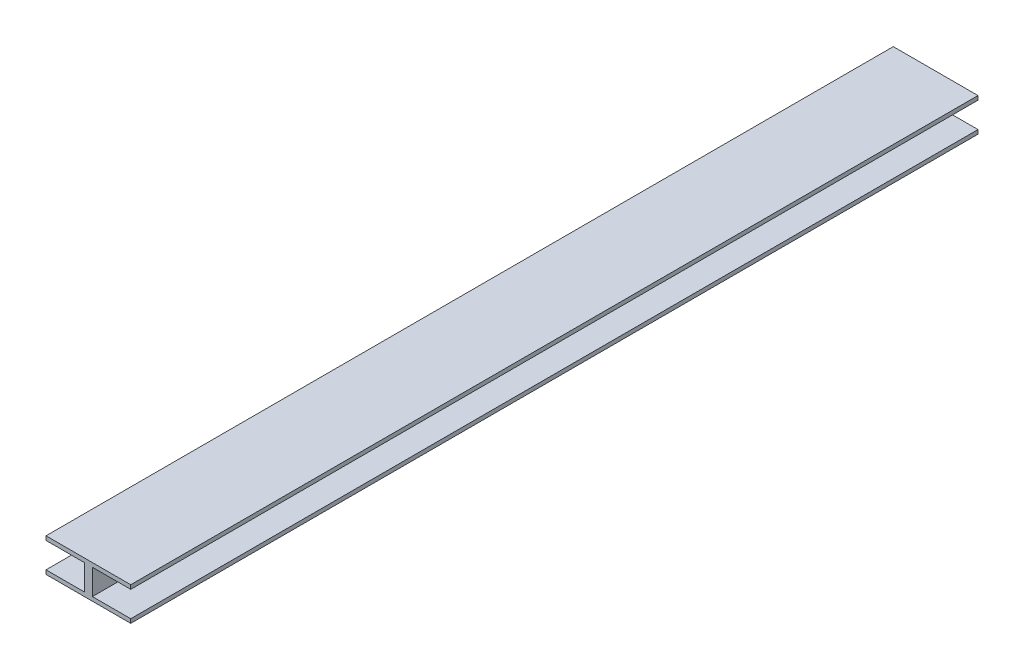
SolidWorks part; units mm, degrees
material "Acero al carbono no aleado"
ref_plane "Alzado" through (0, 0, 0) normal (0, 0, 1) x (1, 0, 0)
ref_plane "Planta" through (0, 0, 0) normal (0, 1, 0) x (1, 0, 0)
ref_plane "Vista lateral" through (0, 0, 0) normal (1, 0, 0) x (0, 0, -1)
sketch "Croquis1" plane through (0, 0, 0) normal (0, 0, 1) x (1, 0, 0)
  line L0 (0, 19.7625) -> (-50, 19.7625)
  line L1 (0, 19.7625) -> (0, -19.7625)
  line L2 (0, -19.7625) -> (-50, -19.7625)
  line L3 (-4.7625, -15) -> (-50, -15)
  line L4 (-4.7625, 15) -> (-4.7625, -15)
  line L5 (-4.7625, 15) -> (-50, 15)
  line L6 (-50, -19.7625) -> (-50, -15)
  line L7 (-50, 19.7625) -> (-50, 15)
  line L8 (10.168, 0) -> (-43.4141, 0) construction
  line L9 (4.7625, 15) -> (4.7625, -15)
  line L10 (4.7625, 15) -> (50, 15)
  line L11 (50, 19.7625) -> (50, 15)
  line L12 (0, 19.7625) -> (50, 19.7625)
  line L13 (0, -19.7625) -> (50, -19.7625)
  line L14 (50, -19.7625) -> (50, -15)
  line L15 (4.7625, -15) -> (50, -15)
  line L16 (0, 19.7625) -> (0, -19.7625)
  line L17 (50, -19.7625) -> (50, -15)
  line L18 (4.7625, -15) -> (4.7625, 15)
  line L19 (50, 15) -> (50, 19.7625)
  dimension "D2" = 50
  dimension "D3" = 15
  dimension "D1" = 4.7625
extrude "Saliente-Extruir1" add sketch "Croquis1" along normal mid plane 1000 contours L8 L9 L10 L11 L12 L1 | L18 L8 L16 L13 L14 L15 | L8 L1 L0 L7 L5 L4 | L16 L8 L4 L3 L6 L2 region at (-19.7803, 15.101, 0) region at (19.7803, 15.101, 0) region at (19.7803, -15.101, 0) region at (-19.7803, -15.101, 0)
